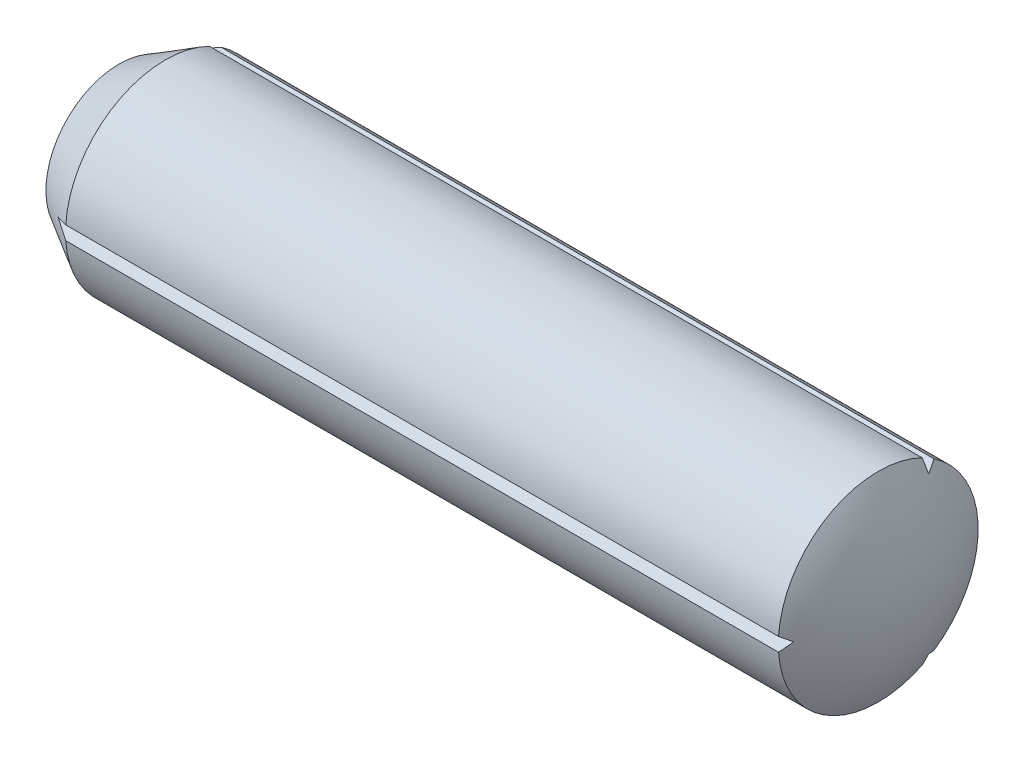
SolidWorks part; units mm, degrees
revolve "Base-Revolve" add sketch "Sketch1" angle 360 about L0
sketch "Sketch1" plane through (0, 0, 0) normal (0, 0, 1) x (1, 0, 0)
  line L0 (-117, 0) -> (21, 0) construction
  line L1 (-92.5, 12.5) -> (-98.295, 9.1543)
  line L2 (-92.5, 12.5) -> (-3.3494, 12.5)
  line L3 (-100, 0) -> (0, 0)
  line L4 (-100, 0) -> (-100, 1.25)
  arc A0 (-98.295, 9.1543) -> (-100, 1.25) centre (-75.0313, 0) ccw
  arc A1 (0, 0) -> (-3.3494, 12.5) centre (-25, 0) ccw
  dimension "D2" = 25
  dimension "D4" = 25
  dimension "Length" = 100
  dimension "D1" = 2.5
  dimension "D3" = 30
  dimension "Chamfer2" = 7.5
ref_plane "Plane1" through (0, 0, 0) normal (0, 0, 1) x (1, 0, 0)
ref_plane "Plane2" through (0, 0, 0) normal (0, 1, 0) x (1, 0, 0)
ref_plane "Plane3" through (0, 0, 0) normal (1, 0, 0) x (0, 0, -1)
sketch "Sketch2" plane through (0, 0, 0) normal (1, 0, 0) x (0, 0, -1)
  line L0 (0, 0) -> (-14, 0) construction
  line L1 (-11.25, 0) -> (-12.5, 0.8753)
  line L2 (-11.25, 0) -> (-12.5, -0.8753)
  line L3 (-12.5, -0.8753) -> (-12.5, 0.8753)
  circle A0 centre (0, 0) radius 11.25 construction
  circle A1 centre (0, 0) radius 12.5 construction
  dimension "D1" = 22.5
  dimension "D2" = 70
  dimension "D3" = 35
extrude "Cut-Extrude1" cut sketch "Sketch2" against normal through all
pattern_circular "CirPattern2" count 3 over 360 about axis through (-117, 0, 0) along (1, 0, 0) of "Cut-Extrude1"
equation "\"D2@Sketch1\" = \"Diameter@Sketch1\""
equation "\"D1@Sketch2\" = \"Diameter@Sketch1\" * .9"
equation "\"D3@Sketch2\" = \"D2@Sketch2\" / 2"
equation "\"D1@Sketch1\" = \"Diameter@Sketch1\" * .1"
equation "\"D4@Sketch1\" = \"Diameter@Sketch1\""
